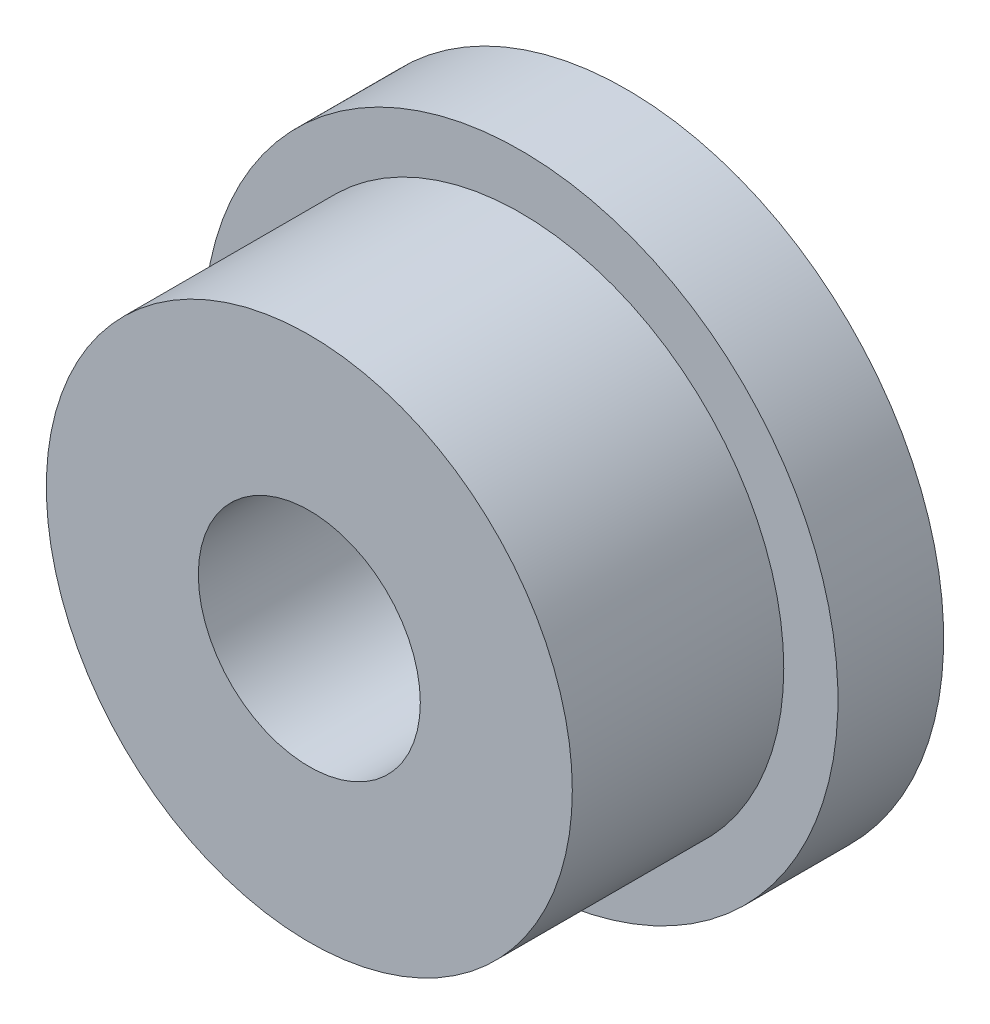
SolidWorks part; units mm, degrees
ref_plane "正面" through (0, 0, 0) normal (0, 0, 1) x (1, 0, 0)
ref_plane "平面" through (0, 0, 0) normal (0, 1, 0) x (1, 0, 0)
ref_plane "右側面" through (0, 0, 0) normal (1, 0, 0) x (0, 0, -1)
sketch "ｽｹｯﾁ1" plane through (0, 0, 0) normal (0, 0, 1) x (1, 0, 0)
  circle A0 centre (0, 0) radius 4.975
  dimension "D1" = 9.95
extrude "ﾎﾞｽ - 押し出し1" add sketch "ｽｹｯﾁ1" along normal blind 4
sketch "ｽｹｯﾁ2" plane through (0, 0, 0) normal (0, 0, -1) x (-1, 0, 0)
  circle A0 centre (0, 0) radius 6
  dimension "D1" = 12
extrude "ﾎﾞｽ - 押し出し2" add sketch "ｽｹｯﾁ2" along normal blind 2 contours A0
sketch "ｽｹｯﾁ3" plane through (0, 0, 4) normal (0, 0, 1) x (1, 0, 0)
  circle A0 centre (0, 0) radius 2.1
  dimension "D1" = 4.2
extrude "ｶｯﾄ - 押し出し1" cut sketch "ｽｹｯﾁ3" against normal through all
sketch "ｽｹｯﾁ4" plane through (0, 0, -2) normal (0, 0, -1) x (-1, 0, 0)
  circle A0 centre (0, 0) radius 4
  dimension "D1" = 8
extrude "ｶｯﾄ - 押し出し2" cut sketch "ｽｹｯﾁ4" against normal blind 3
